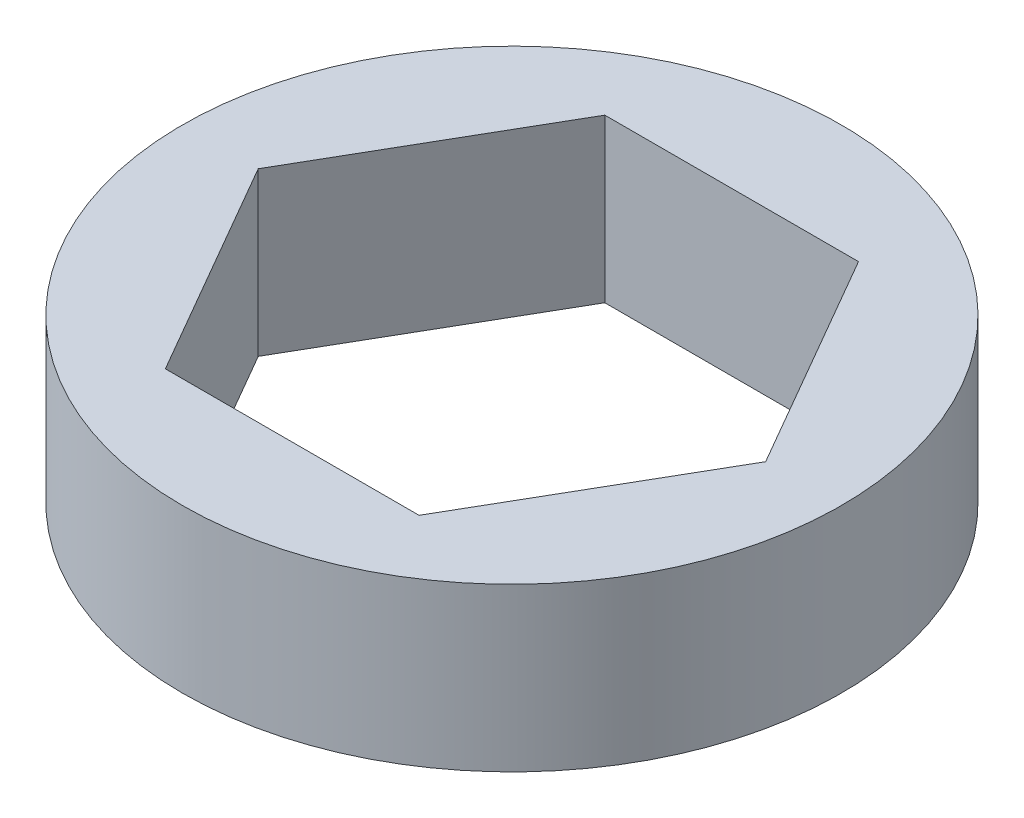
SolidWorks part; units mm, degrees
material "PET"
ref_plane "Front Plane" through (0, 0, 0) normal (0, 0, 1) x (1, 0, 0)
ref_plane "Top Plane" through (0, 0, 0) normal (0, 1, 0) x (1, 0, 0)
ref_plane "Right Plane" through (0, 0, 0) normal (1, 0, 0) x (0, 0, -1)
sketch "Sketch1" plane through (0, 0, 0) normal (0, 1, 0) x (1, 0, 0)
  line L1 (7.3323, 0) -> (3.6662, 6.35)
  line L2 (3.6662, 6.35) -> (-3.6662, 6.35)
  line L3 (-3.6662, 6.35) -> (-7.3323, 0)
  line L4 (-7.3323, 0) -> (-3.6662, -6.35)
  line L5 (-3.6662, -6.35) -> (3.6662, -6.35)
  line L6 (3.6662, -6.35) -> (7.3323, 0)
  circle A0 centre (0, 0) radius 6.35 construction
  circle A1 centre (0, 0) radius 9.525
  dimension "D1" = 19.05
  dimension "D2" = 12.7
extrude "Boss-Extrude1" add sketch "Sketch1" along normal blind 4.6965
